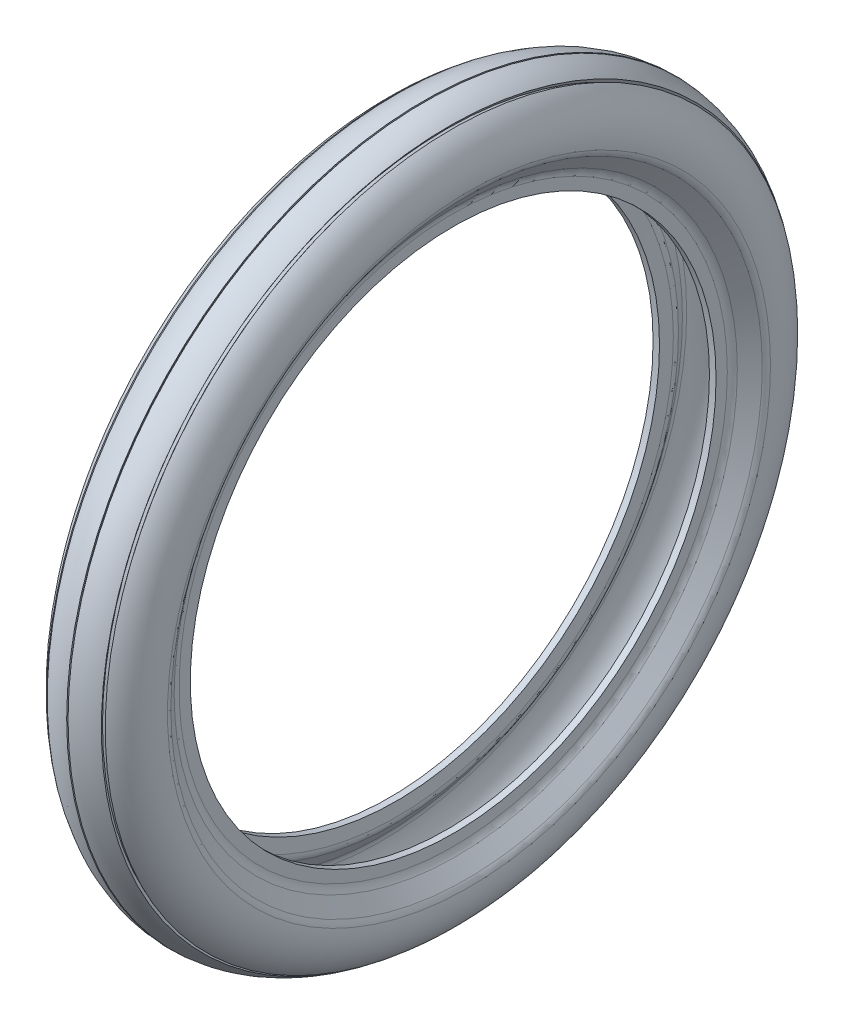
SolidWorks part; units mm, degrees
ref_plane "Front Plane" through (0, 0, 0) normal (0, 0, 1) x (1, 0, 0)
ref_plane "Top Plane" through (0, 0, 0) normal (0, 1, 0) x (1, 0, 0)
ref_plane "Right Plane" through (0, 0, 0) normal (1, 0, 0) x (0, 0, -1)
sketch "Sketch1" plane through (0, 0, 0) normal (0, 0, 1) x (1, 0, 0)
  line L0 (-23.5756, 207.417) -> (-18.1673, 207.2846)
  line L1 (28.6465, 219.412) -> (41.1189, 235.5965) construction
  line L3 (28.6465, 206.7777) -> (28.6465, 216.0059)
  line L4 (30.7256, 222.11) -> (39.6122, 233.6414)
  line L8 (25.3158, 223.9527) -> (34.3975, 235.7373)
  line L9 (23.2366, 206.7777) -> (23.2366, 217.8486)
  line L11 (28.6465, 206.7777) -> (23.2366, 206.7777)
  line L15 (4.3623, 283.7385) -> (3.4456, 281.4418)
  line L16 (23.2319, 273.311) -> (25.276, 276.2682)
  line L20 (24.9151, 272.0553) -> (23.2319, 273.311)
  line L21 (27.0916, 274.8858) -> (24.9151, 272.0553)
  line L23 (23.2366, 221.2547) -> (36.0474, 237.8783) construction
  line L24 (28.6465, 206.7777) -> (28.6465, 219.412) construction
  line L25 (23.2366, 206.7777) -> (23.2366, 221.2547) construction
  line L26 (-15.4013, 219.3356) -> (-31.4682, 234.8821) construction
  line L27 (-20.9005, 217.1289) -> (-36.2685, 231.9991) construction
  line L28 (-15.7326, 210.7649) -> (-15.4013, 219.3356) construction
  line L29 (-21.1384, 210.9739) -> (-20.9005, 217.1289) construction
  line L30 (0, 0) -> (0, -8.5) construction
  line L31 (0, 0) -> (3.9759, 324.7586) construction
  line L32 (48.0366, -8.5) -> (-48.0366, -8.5) construction
  line L33 (-23.5756, 207.417) -> (-23.3497, 216.6425)
  line L34 (-25.2788, 222.7957) -> (-33.8804, 234.5411)
  line L35 (-20.3538, 275.4666) -> (-18.2473, 272.5838)
  line L36 (-16.5338, 273.7978) -> (-18.5049, 276.8042)
  line L38 (5.3623, 283.6203) -> (3.4456, 281.4418)
  line L39 (-18.2473, 272.5838) -> (-16.5338, 273.7978)
  line L40 (-19.8254, 224.5054) -> (-28.6159, 236.5088)
  line L41 (-18.1673, 207.2846) -> (-17.8963, 218.3521)
  arc A0 (41.6012, 238.4057) -> (27.0916, 274.8858) centre (1.9619, 243.7651) ccw
  arc A1 (36.446, 241.0592) -> (3.4075, 278.325) centre (1.9619, 243.7651) ccw
  arc A3 (41.1189, 235.5965) -> (-36.2685, 231.9991) centre (1.9619, 243.7651) ccw construction
  arc A5 (41.6012, 238.4057) -> (39.6122, 233.6414) centre (31.6914, 239.7455) cw
  arc A6 (36.0474, 237.8783) -> (-31.4682, 234.8821) centre (1.9619, 243.7651) ccw construction
  arc A7 (36.446, 241.0592) -> (34.3975, 235.7373) centre (26.4766, 241.8414) cw
  arc A8 (30.7256, 222.11) -> (28.6465, 216.0059) centre (38.6465, 216.0059) ccw
  arc A9 (25.3158, 223.9527) -> (23.2366, 217.8486) centre (33.2366, 217.8486) ccw
  arc A14 (25.276, 276.2682) -> (5.3623, 283.6203) centre (1.9619, 243.7651) ccw
  arc A15 (-25.2788, 222.7957) -> (-23.3497, 216.6425) centre (-33.3467, 216.8873) cw
  arc A16 (-35.7521, 239.3527) -> (-33.8804, 234.5411) centre (-25.8125, 240.4495) ccw
  arc A17 (-18.5049, 276.8042) -> (4.3623, 283.7385) centre (4.0065, 243.7401) cw
  arc A18 (-35.7521, 239.3527) -> (-20.3538, 275.4666) centre (4.0065, 243.7401) cw
  arc A19 (-30.5335, 241.8792) -> (3.4075, 278.325) centre (4.0065, 243.7401) cw
  arc A20 (-30.5335, 241.8792) -> (-28.6159, 236.5088) centre (-20.548, 242.4171) ccw
  arc A21 (-19.8254, 224.5054) -> (-17.8963, 218.3521) centre (-27.8933, 218.597) cw
  point P62 (0, -8.5)
  dimension "D4" = 8.5
  dimension "D2" = 1
  dimension "D1" = 40
  dimension "D5" = 10
  dimension "D3" = 26
  dimension "D6" = 252.2651
revolve "Revolve1" add sketch "Sketch1" angle 360 about L32
